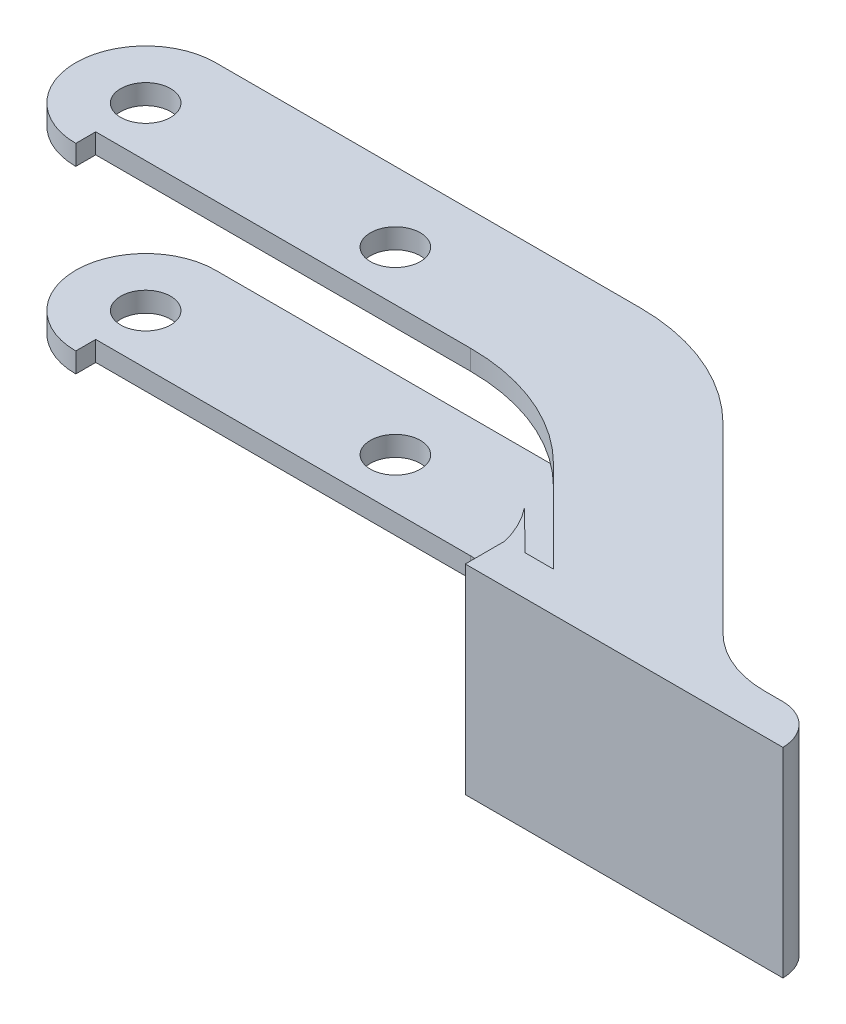
SolidWorks part; units mm, degrees
ref_plane "Front Plane" through (0, 0, 0) normal (0, 0, 1) x (1, 0, 0)
ref_plane "Top Plane" through (0, 0, 0) normal (0, 1, 0) x (1, 0, 0)
ref_plane "Right Plane" through (0, 0, 0) normal (1, 0, 0) x (0, 0, -1)
sketch "Sketch1" plane through (0, 0, 0) normal (0, 1, 0) x (1, 0, 0)
  line L0 (0, 0) -> (25, 0) construction
  line L1 (0, 7) -> (25, 7)
  line L2 (0, -7) -> (25, -7)
  arc A0 (0, 7) -> (0, -7) centre (0, 0) ccw
  arc A1 (25, -7) -> (25, 7) centre (25, 0) ccw
  circle A2 centre (0, 0) radius 2.5
  circle A3 centre (25, 0) radius 2.5
  point P3 (12.5, 0)
  dimension "D1" = 5
  dimension "D2" = 5
  dimension "D3" = 25
  dimension "D4" = 14
extrude "Boss-Extrude1" add sketch "Sketch1" along normal blind 2
sketch "Sketch2" plane through (0, 0, 0) normal (0, -1, 0) x (1, 0, 0)
  line L0 (25, 7) -> (45, 7) construction
  line L1 (25, -7) -> (45, -7) construction
  line L2 (45, 7) -> (61.9706, 23.9706) construction
  line L3 (61.9706, 23.9706) -> (71.8701, 14.0711) construction
  line L4 (71.8701, 14.0711) -> (50.799, -7) construction
  line L5 (50.799, -7) -> (45, -7) construction
  dimension "D1" = 20
  dimension "D2" = 14
  dimension "D3" = 24
  dimension "D4" = 135
sketch "Sketch3" plane through (0, 0, 0) normal (0, -1, 0) x (-1, 0, 0)
  line L0 (-25, -7) -> (-36.7157, -7)
  line L1 (-50.8579, -12.8579) -> (-61.9706, -23.9706)
  line L2 (-61.9706, -23.9706) -> (-81.7696, -23.9706)
  line L3 (-71.8701, -14.0711) -> (-81.7696, -23.9706)
  line L4 (-71.8701, -14.0711) -> (-56.6569, 1.1421)
  line L5 (-42.5147, 7) -> (-25, 7)
  arc A0 (-42.5147, 7) -> (-56.6569, 1.1421) centre (-42.5147, -13) ccw
  arc A1 (-36.7157, -7) -> (-50.8579, -12.8579) centre (-36.7157, -27) ccw
  arc A2 (-25, 7) -> (-25, -7) centre (-25, 0) ccw
  point P15 (-50.799, 7)
  point P18 (-45, -7)
  dimension "D1" = 20
  dimension "D2" = 20
extrude "Boss-Extrude2" add sketch "Sketch3" against normal blind 2
sketch "Sketch4" plane through (0, 2, 0) normal (0, 1, 0) x (1, 0, 0)
  line L10 (55.9706, -20.004) -> (87.7696, -20.004)
  line L11 (55.9706, -20.004) -> (55.9706, -23.9706)
  line L12 (55.9706, -23.9706) -> (87.7696, -23.9706)
  line L13 (87.7696, -20.004) -> (87.7696, -23.9706)
  dimension "D1" = 6
  dimension "D2" = 6
extrude "Boss-Extrude3" add sketch "Sketch4" along normal blind 18 and the other way blind 2
sketch "Sketch8" plane through (0, 0, 0) normal (0, -1, 0) x (1, 0, 0)
  line L0 (0, 0) -> (25, 0) construction
  line L1 (0, 5) -> (25, 5)
  line L4 (25, 5) -> (37.5442, 5)
  line L5 (60.8324, 20.004) -> (51.6863, 10.8579)
  line L6 (58.004, 20.004) -> (50.8579, 12.8579) construction
  line L7 (58.004, 20.004) -> (60.8324, 20.004)
  line L8 (58.004, 20.004) -> (50.5285, 12.6973)
  line L9 (36.5488, 7) -> (0, 7)
  line L10 (0, 7) -> (0, 5)
  arc A2 (50.5285, 12.6973) -> (36.5488, 7) centre (36.5488, 27) cw
  arc A3 (51.6863, 10.8579) -> (37.5442, 5) centre (37.5442, 25) cw
  point P4 (12.5, 0)
  point P23 (44.6996, 7)
  dimension "D3" = 20
  dimension "D4" = 20
  dimension "D2" = 2
ref_plane "Plane1" through (0, 10, 0) normal (0, 1, 0) x (1, 0, 0)
mirror "Mirror1" about plane through (0, 10, 0) normal (0, 1, 0) of "Boss-Extrude2", "Boss-Extrude1"
sketch "Sketch6" plane through (0, 20, 0) normal (0, 1, 0) x (1, 0, 0)
  line L0 (25, 0) -> (0, 0) construction
  line L1 (25, -7) -> (0, -7)
  line L2 (25, 7) -> (0, 7)
  arc A0 (25, -7) -> (25, 7) centre (25, 0) ccw
  arc A1 (0, 7) -> (0, -7) centre (0, 0) ccw
  circle A2 centre (0, 0) radius 2.5
  circle A3 centre (25, 0) radius 2.5
  point P4 (12.5, 0)
  dimension "D1" = 14
extrude "Boss-Extrude5" add sketch "Sketch6" against normal blind 2
fillet "Fillet1" radius 10 2 edges at (58.004, 1, 20.004) (58.004, 19, 20.004)
fillet "Fillet2" radius 10 2 edges at (77.803, 19, 20.004) (77.803, 1, 20.004)
fillet "Fillet4" radius 4 1 edges at (87.7696, 10, 20.004)
sketch "Sketch7" plane through (0, 2, 0) normal (0, 1, 0) x (1, 0, 0)
  line L0 (0, 0) -> (25, 0) construction
  line L1 (0, 7) -> (25, 7)
  line L3 (0, 0) -> (25, 0) construction
  line L4 (0, 5) -> (25, 5)
  line L6 (-7, 0) -> (-5, 0)
  line L9 (25, 7) -> (42.5147, 7)
  line L10 (74.8741, -17.0751) -> (56.6569, 1.1421)
  line L11 (74.9746, -20.004) -> (81.9451, -20.004)
  line L16 (25, 5) -> (41.6863, 5)
  line L17 (71.0679, -16.0974) -> (55.8284, -0.8579)
  line L19 (71.0679, -16.0974) -> (74.9746, -20.004)
  arc A0 (0, 7) -> (-7, 0) centre (0, 0) ccw
  arc A2 (0, 5) -> (-5, 0) centre (0, 0) ccw
  arc A4 (56.6569, 1.1421) -> (42.5147, 7) centre (42.5147, -13) ccw
  arc A5 (55.8284, -0.8579) -> (41.6863, 5) centre (41.6863, -15) ccw
  spline S0 degree 3 poles (74.8741, -17.0751) (76.6185, -18.7453) (78.6848, -19.8172) (81.9451, -20.004) knots 0 0 0 0 1 1 1 1
  point P4 (12.5, 0)
  point P12 (12.5, 0)
  dimension "D1" = 7
  dimension "D4" = 20
  dimension "D5" = 20
  dimension "D2" = 2
  dimension "D3" = 2
extrude "Cut-Extrude1" cut sketch "Sketch8" against normal through all
